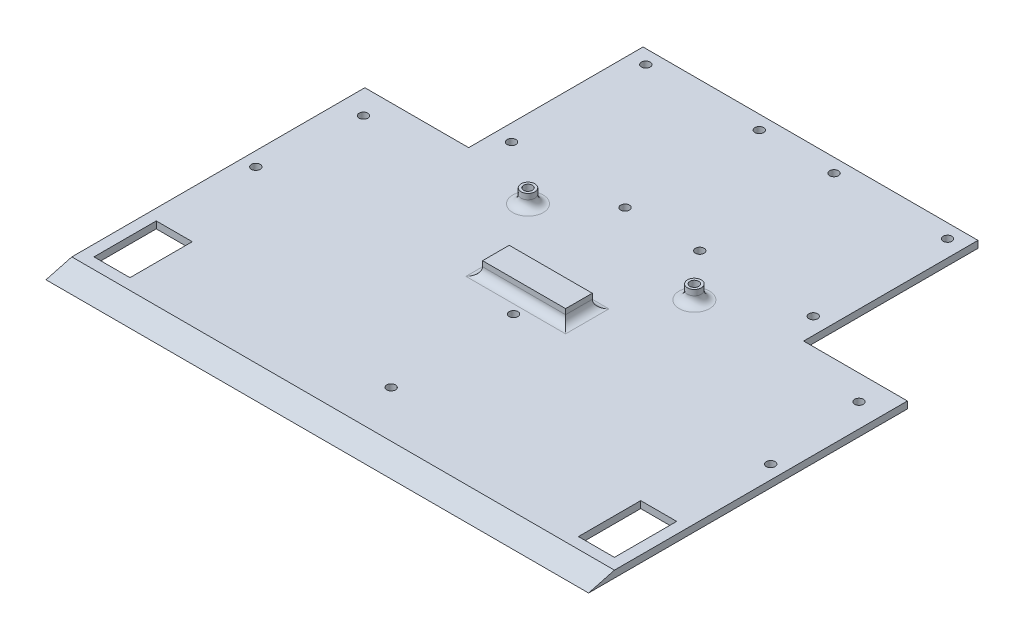
SolidWorks part; units mm, degrees
ref_plane "Alzado" through (0, 0, 0) normal (0, 0, 1) x (1, 0, 0)
ref_plane "Planta" through (0, 0, 0) normal (0, 1, 0) x (1, 0, 0)
ref_plane "Vista lateral" through (0, 0, 0) normal (1, 0, 0) x (0, 0, -1)
sketch "Croquis1" plane through (0, 0, 0) normal (1, 0, 0) x (0, 0, -1)
  line L0 (0, 0) -> (178.17, 0)
  line L1 (178.17, 0) -> (178.17, 2.5)
  line L2 (178.17, 2.5) -> (9.3301, 2.5)
  line L3 (0, 0) -> (9.3301, 2.5)
  dimension "D1" = 178.17
  dimension "D2" = 2.5
  dimension "D3" = 165
extrude "Saliente-Extruir1" add sketch "Croquis1" along normal blind 196
sketch "Croquis2" plane through (0, 0, 0) normal (0, -1, 0) x (-1, 0, 0)
  line L1 (-37.5, 115.1801) -> (0, 115.1801)
  line L2 (-37.5, 115.1801) -> (-37.5, 178.17)
  line L3 (-37.5, 178.17) -> (0, 178.17)
  line L4 (0, 115.1801) -> (0, 178.17)
  line L5 (-37.5, 115.1801) -> (0, 178.17) construction
  line L6 (-37.5, 178.17) -> (0, 115.1801) construction
  line L7 (-158.5, 115.1801) -> (-196, 115.1801)
  line L8 (-158.5, 115.1801) -> (-158.5, 178.17)
  line L9 (-158.5, 178.17) -> (-196, 178.17)
  line L10 (-196, 115.1801) -> (-196, 178.17)
  line L11 (-158.5, 115.1801) -> (-196, 178.17) construction
  line L12 (-158.5, 178.17) -> (-196, 115.1801) construction
  point P4 (-18.75, 146.6751)
  point P11 (-177.25, 146.6751)
extrude "Cortar-Extruir1" cut sketch "Croquis2" against normal up to next
sketch "Croquis4" plane through (0, 2.5, 0) normal (0, 1, 0) x (1, 0, 0)
  line L7 (4, 13.3301) -> (17, 13.3301)
  line L8 (4, 13.3301) -> (4, 35.8301)
  line L9 (4, 35.8301) -> (17, 35.8301)
  line L10 (17, 13.3301) -> (17, 35.8301)
  line L11 (4, 13.3301) -> (17, 35.8301) construction
  line L12 (4, 35.8301) -> (17, 13.3301) construction
  point P9 (10.5, 24.5801)
  dimension "D3" = 22.5
  dimension "D4" = 13
extrude "Cortar-Extruir2" cut sketch "Croquis4" against normal up to next
ref_plane "Plano1" through (98, 0, 0) normal (1, 0, 0) x (0, 0, -1)
mirror "Simetría1" about plane through (98, 0, 0) normal (1, 0, 0) of "Cortar-Extruir2"
sketch "Sketch1" plane through (0, 2.5, 0) normal (0, 1, 0) x (1, 0, 0)
  circle A0 centre (187.5, 106.1801) radius 1.585
  circle A1 centre (8.5, 106.1801) radius 1.585
extrude "Cut-Extrude1" cut sketch "Sketch1" against normal up to next
sketch "Sketch2" plane through (0, 2.5, 0) normal (0, 1, 0) x (1, 0, 0)
  circle A0 centre (98.5, 26.1801) radius 1.585
extrude "Cut-Extrude2" cut sketch "Sketch2" against normal up to next
sketch "Sketch3" plane through (0, 2.5, 0) normal (0, 1, 0) x (1, 0, 0)
  circle A0 centre (111.5, 124.67) radius 1.585
  circle A1 centre (152.5, 124.67) radius 1.585
  circle A2 centre (152.5, 173.17) radius 1.585
  circle A3 centre (111.5, 173.17) radius 1.585
  circle A4 centre (84.5, 173.17) radius 1.585
  circle A5 centre (43.5, 173.17) radius 1.585
  circle A6 centre (43.5, 124.67) radius 1.585
  circle A7 centre (84.5, 124.67) radius 1.585
extrude "Cut-Extrude3" cut sketch "Sketch3" against normal up to next
sketch "Sketch4" plane through (0, 2.5, 0) normal (0, 1, 0) x (1, 0, 0)
  circle A0 centre (125.8764, 108.3369) radius 1.6
  circle A1 centre (65.7764, 108.3369) radius 1.6
  circle A2 centre (65.7764, 108.3369) radius 2.5
  circle A3 centre (125.8764, 108.3369) radius 2.5
  dimension "D1" = 5
  dimension "D2" = 5
extrude "Boss-Extrude1" add sketch "Sketch4" along normal blind 5
sketch "Sketch5" plane through (0, 2.5, 0) normal (0, 1, 0) x (1, 0, 0)
  line L1 (80.272, 87.0616) -> (110.272, 87.0616)
  line L2 (80.272, 87.0616) -> (80.272, 77.4239)
  line L3 (80.272, 77.4239) -> (110.272, 77.4239)
  line L4 (110.272, 87.0616) -> (110.272, 77.4239)
  line L5 (80.272, 87.0616) -> (110.272, 77.4239) construction
  line L6 (80.272, 77.4239) -> (110.272, 87.0616) construction
  point P4 (96.9958, 82.487)
extrude "Boss-Extrude2" add sketch "Sketch5" along normal blind 4.9
sketch "Sketch6" plane through (0, 2.5, 0) normal (0, 1, 0) x (1, 0, 0)
  circle A0 centre (125.8764, 108.3369) radius 1.6
  circle A1 centre (65.7764, 108.3369) radius 1.6
extrude "Cut-Extrude4" cut sketch "Sketch6" against normal blind 4.9
sketch "Sketch7" plane through (0, 2.5, 0) normal (0, 1, 0) x (1, 0, 0)
  circle A0 centre (5.0671, 70.7278) radius 1.585
  circle A1 centre (97.6819, 71.2085) radius 1.585
  circle A2 centre (191.0671, 70.7278) radius 1.585
extrude "Cut-Extrude5" cut sketch "Sketch7" against normal blind 10
fillet "Fillet1" radius 3 6 edges at (80.272, 2.5, -82.2427) (95.272, 2.5, -87.0616) (110.272, 2.5, -82.2427) (95.272, 2.5, -77.4239) (65.7764, 2.5, -110.8369) (125.8764, 2.5, -110.8369)
